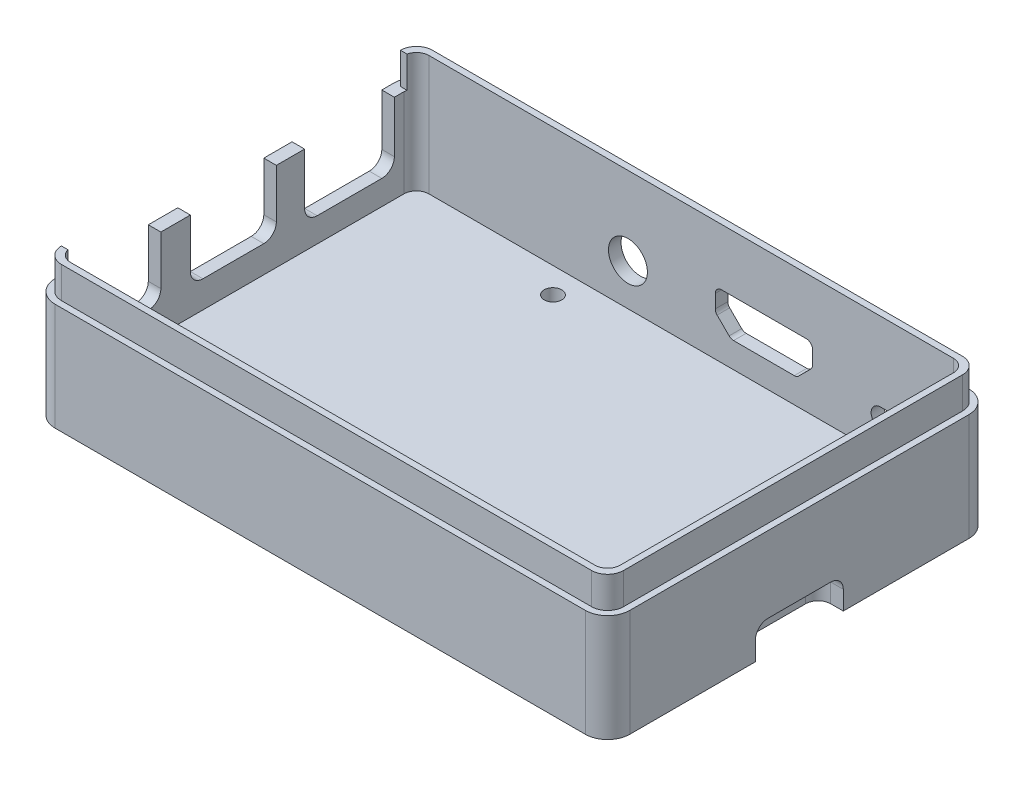
SolidWorks part; units mm, degrees
material "Custom Plastic"
ref_plane "Спереди" through (0, 0, 0) normal (0, 0, 1) x (1, 0, 0)
ref_plane "Сверху" through (0, 0, 0) normal (0, 1, 0) x (1, 0, 0)
ref_plane "Справа" through (0, 0, 0) normal (1, 0, 0) x (0, 0, -1)
ref_plane "Plane1" through (0, 0, 63.69) normal (0, 0, 1) x (1, 0, 0)
sketch "Sketch1" plane through (0, 0, 63.69) normal (0, 0, 1) x (1, 0, 0)
  line L0 (42.5, 14.1) -> (-44.05, 14.1)
  line L1 (-44.05, 14.1) -> (-44.05, -3)
  line L2 (-44.05, -3) -> (42.5, -3)
  line L3 (42.5, -3) -> (42.5, 14.1)
extrude "Boss-Extrude1" add sketch "Sketch1" against normal blind 14
sketch "Sketch2" plane through (0, 0, 49.69) normal (0, 0, -1) x (-1, 0, 0)
  line L0 (-44.5, 14.1) -> (44.05, 14.1)
  line L1 (44.05, 14.1) -> (44.05, -3)
  line L2 (44.05, -3) -> (-44.5, -3)
  line L3 (-44.5, -3) -> (-44.5, 14.1)
extrude "Boss-Extrude2" add sketch "Sketch2" along normal blind 23.55
sketch "Sketch3" plane through (44.5, 0, 0) normal (1, 0, 0) x (0, 0, -1)
  line L0 (-63.69, 14.1) -> (-26.14, 14.1)
  line L1 (-26.14, 14.1) -> (-26.14, -3)
  line L2 (-26.14, -3) -> (-63.69, -3)
  line L3 (-63.69, -3) -> (-63.69, 14.1)
extrude "Boss-Extrude3" add sketch "Sketch3" along normal blind 2
sketch "Sketch4" plane through (0, 0, 63.69) normal (0, 0, 1) x (1, 0, 0)
  line L0 (-44.05, 14.1) -> (46.5, 14.1)
  line L1 (46.5, 14.1) -> (46.5, -3)
  line L2 (46.5, -3) -> (-44.05, -3)
  line L3 (-44.05, -3) -> (-44.05, 14.1)
extrude "Boss-Extrude4" add sketch "Sketch4" along normal blind 23.55
sketch "Sketch5" plane through (0, -3, 0) normal (0, -1, 0) x (1, 0, 0)
  line L0 (44.5, 63.69) -> (44.5, 49.69)
  line L1 (44.5, 49.69) -> (46.5, 49.69)
  line L2 (46.5, 49.69) -> (46.5, 63.69)
  line L3 (46.5, 63.69) -> (44.5, 63.69)
extrude "Cut-Extrude1" cut sketch "Sketch5" against normal blind 3
sketch "Sketch6" plane through (0, 14.1, 0) normal (0, 1, 0) x (-1, 0, 0)
  line L0 (43.05, 29.69) -> (43.05, 83.69)
  line L1 (43.05, 83.69) -> (-44.5, 83.69)
  line L2 (-44.5, 83.69) -> (-44.5, 63.69)
  line L3 (-44.5, 63.69) -> (-42.5, 63.69)
  line L4 (-42.5, 63.69) -> (-42.5, 49.69)
  line L5 (-42.5, 49.69) -> (-44.5, 49.69)
  line L6 (-44.5, 49.69) -> (-44.5, 29.69)
  line L7 (-44.5, 29.69) -> (43.05, 29.69)
extrude "Cut-Extrude2" cut sketch "Sketch6" against normal blind 14.1
sketch "Sketch7" plane through (0, 0, 0) normal (0, -1, 0) x (1, 0, 0)
  line L0 (44.5, 63.69) -> (44.5, 49.69)
  line L1 (44.5, 49.69) -> (46.5, 49.69)
  line L2 (46.5, 49.69) -> (46.5, 63.69)
  line L3 (46.5, 63.69) -> (44.5, 63.69)
extrude "Cut-Extrude3" cut sketch "Sketch7" against normal blind 2
sketch "Sketch8" plane through (0, 14.1, 0) normal (0, 1, 0) x (-1, 0, 0)
  line L0 (-44.5, 83.69) -> (-44.5, 29.69)
  line L1 (-44.5, 29.69) -> (44.05, 29.69)
  line L2 (41.5, 27.14) -> (-45.5, 27.14)
  line L3 (-45.5, 27.14) -> (-45.5, 86.24)
  line L4 (-45.5, 86.24) -> (41.5, 86.24)
  line L5 (44.05, 83.69) -> (-44.5, 83.69)
  arc A0 (44.05, 29.69) -> (41.5, 27.14) centre (41.5, 29.69) cw
  arc A1 (41.5, 86.24) -> (44.05, 83.69) centre (41.5, 83.69) cw
extrude "Boss-Extrude5" add sketch "Sketch8" along normal blind 5
sketch "Sketch9" plane through (0, 0, 83.69) normal (0, 0, -1) x (-1, 0, 0)
  line L0 (43.05, 19.1) -> (-44.5, 19.1)
  line L1 (-44.5, 19.1) -> (-44.5, 0)
  line L2 (-44.5, 0) -> (43.05, 0)
  line L3 (43.05, 0) -> (43.05, 19.1)
extrude "Cut-Extrude4" cut sketch "Sketch9" against normal blind 1.55
sketch "Sketch10" plane through (-44.05, 0, 0) normal (-1, 0, 0) x (0, 0, 1)
  line L0 (87.24, 14.1) -> (87.24, -3)
  line L1 (87.24, -3) -> (26.14, -3)
  line L2 (26.14, -3) -> (26.14, 14.1)
  line L3 (26.14, 14.1) -> (87.24, 14.1)
extrude "Boss-Extrude6" add sketch "Sketch10" along normal blind 1
ref_plane "Plane2" through (0, 0, 28.14) normal (0, 0, -1) x (-1, 0, 0)
sketch "Sketch11" plane through (0, 0, 28.14) normal (0, 0, -1) x (-1, 0, 0)
  line L0 (-44.5, 0) -> (43.05, 0)
  line L1 (43.05, 0) -> (43.05, 19.1)
  line L2 (43.05, 19.1) -> (-44.5, 19.1)
  line L3 (-44.5, 19.1) -> (-44.5, 0)
extrude "Cut-Extrude5" cut sketch "Sketch11" against normal up to next
sketch "Sketch12" plane through (-43.05, 0, 0) normal (1, 0, 0) x (0, 0, -1)
  line L0 (-68.8557, 14.1) -> (-82.5557, 14.1)
  line L1 (-82.5557, 14.1) -> (-82.5557, 4.3)
  line L2 (-82.5557, 4.3) -> (-68.8557, 4.3)
  line L3 (-68.8557, 4.3) -> (-68.8557, 14.1)
extrude "Cut-Extrude6" cut sketch "Sketch12" against normal through all
sketch "Sketch13" plane through (-43.05, 0, 0) normal (1, 0, 0) x (0, 0, -1)
  line L0 (-50.4557, 14.1) -> (-64.1557, 14.1)
  line L1 (-64.1557, 14.1) -> (-64.1557, 4.3)
  line L2 (-64.1557, 4.3) -> (-50.4557, 4.3)
  line L3 (-50.4557, 4.3) -> (-50.4557, 14.1)
extrude "Cut-Extrude7" cut sketch "Sketch13" against normal through all
sketch "Sketch14" plane through (-43.05, 0, 0) normal (1, 0, 0) x (0, 0, -1)
  line L0 (-31.6547, 14.1) -> (-45.9547, 14.1)
  line L1 (-45.9547, 14.1) -> (-45.9547, 3.9)
  line L2 (-45.9547, 3.9) -> (-31.6547, 3.9)
  line L3 (-31.6547, 3.9) -> (-31.6547, 14.1)
extrude "Cut-Extrude8" cut sketch "Sketch14" against normal through all
sketch "Sketch16" plane through (0, 0, 28.14) normal (0, 0, 1) x (1, 0, 0)
  line L0 (20.0578, 10.08) -> (4.5578, 10.08)
  line L1 (4.5578, 10.08) -> (4.5578, 6.53)
  line L2 (4.5578, 6.53) -> (7.0578, 4.03)
  line L3 (7.0578, 4.03) -> (17.5578, 4.03)
  line L4 (17.5578, 4.03) -> (20.0578, 6.53)
  line L5 (20.0578, 6.53) -> (20.0578, 10.08)
extrude "Cut-Extrude10" cut sketch "Sketch16" against normal through all
sketch "Sketch17" plane through (0, 0, 26.14) normal (0, 0, -1) x (-1, 0, 0)
  line L0 (-36.3834, 5.068) -> (-30.8834, 5.068) construction
  line L1 (-36.3834, 6.568) -> (-30.8834, 6.568)
  line L2 (-36.3834, 3.568) -> (-30.8834, 3.568)
  arc A0 (-36.3834, 6.568) -> (-36.3834, 3.568) centre (-36.3834, 5.068) ccw
  arc A1 (-30.8834, 3.568) -> (-30.8834, 6.568) centre (-30.8834, 5.068) ccw
  point P2 (-33.6334, 5.068)
  point P11 (-36.3834, 5.068)
  point P12 (-30.8834, 5.068)
  dimension "D1" = 3
  dimension "D2" = 5.5
extrude "Cut-Extrude11" cut sketch "Sketch17" against normal up to next
hole_wizard "Ø2.8 (2.8) Diameter Hole1" positions "Sketch19" profile "Sketch18" hole size "Ø2.8" standard "ISO" end condition through all
sketch "Sketch19" plane through (0, 0, 0) normal (0, 1, 0) x (1, 0, 0)
  point P0 (40.75, -81.19)
  point P1 (40.75, -32.19)
  point P2 (-17.25, -32.19)
  point P3 (-17.25, -81.19)
sketch "Sketch18" plane through (40.75, 0, 81.19) normal (1, 0, 0) x (0, 0, 1)
  line L0 (0, 0) -> (0, 3)
  line L1 (0, 3) -> (1.4, 3)
  line L2 (1.4, 3) -> (1.4, 0)
  line L5 (1.4, 0) -> (0, 0)
  line L11 (0, -6.35) -> (0, 107.95) construction
  dimension "Thru Hole Dia." = 2.8
  dimension "Thru Hole Depth" = 3
hole_wizard "Ø6.2 (6.2) Diameter Hole1" positions "Sketch21" profile "Sketch20" hole size "Ø6.2" standard "ANSI Metric" end condition up to next
sketch "Sketch21" plane through (0, 0, 26.14) normal (0, 0, -1) x (-1, 0, 0)
  point P0 (9.3535, 6.6)
sketch "Sketch20" plane through (-9.3535, 6.6, 26.14) normal (1, 0, 0) x (0, 1, 0)
  line L0 (0, 0) -> (0, 2)
  line L1 (0, 2) -> (3.1, 2)
  line L2 (3.1, 2) -> (3.1, 0)
  line L5 (3.1, 0) -> (0, 0)
  line L11 (0, -6.35) -> (0, 107.95) construction
  dimension "Thru Hole Dia." = 6.2
  dimension "Thru Hole Depth" = 2
fillet "Fillet1" radius 1 6 edges at (7.0578, 4.03, 27.14) (20.0578, 6.53, 27.14) (4.5578, 6.53, 27.14) (4.5578, 10.08, 27.14) (20.0578, 10.08, 27.14) (17.5578, 4.03, 27.14) tangent propagation no
fillet "Fillet2" radius 2 14 edges at (42.5, -1.5, 63.69) (-44.05, 4.3, 82.5557) (45.5, 2, 63.69) (-44.05, 4.3, 64.1557) (-43.05, 9.55, 85.24) (44.5, 9.55, 85.24) (42.5, -1.5, 49.69) (-44.05, 4.3, 50.4557) (45.5, 2, 49.69) (-44.05, 3.9, 45.9547) (-44.05, 4.3, 68.8557) (-44.05, 3.9, 31.6547) (44.5, 9.55, 28.14) (-43.05, 9.55, 28.14) tangent propagation no
fillet "Fillet3" radius 2.55 2 edges at (45.5, 16.6, 86.24) (45.5, 16.6, 27.14) tangent propagation no
fillet "Fillet4" radius 3.55 4 edges at (46.5, 5.55, 87.24) (-45.05, 5.55, 87.24) (46.5, 5.55, 26.14) (-45.05, 5.55, 26.14) tangent propagation no
